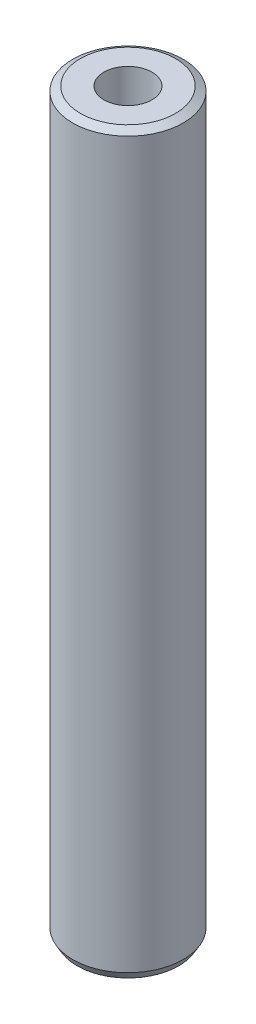
SolidWorks part; units mm, degrees
ref_plane "Front Plane" through (0, 0, 0) normal (0, 0, 1) x (1, 0, 0)
ref_plane "Top Plane" through (0, 0, 0) normal (0, 1, 0) x (1, 0, 0)
ref_plane "Right Plane" through (0, 0, 0) normal (1, 0, 0) x (0, 0, -1)
sketch "Sketch1" plane through (0, 0, 0) normal (0, 1, 0) x (1, 0, 0)
  circle A0 centre (0, 0) radius 45
  dimension "SHAFT_OD" = 90
extrude "Boss-Extrude1" add sketch "Sketch1" along normal blind 600
sketch "Sketch2" plane through (0, 0, 0) normal (0, 1, 0) x (1, 0, 0)
  circle A0 centre (0, 0) radius 19.588
  dimension "BORE_D" = 39.1761
extrude "Cut-Extrude1" cut sketch "Sketch2" along normal through all
chamfer "Chamfer1" distance 3.6153 angle 60 2 edges at (0, 600, 45) (0, 0, 45) first distance on face at (0, 600, 45) first distance on face at (0, 0, 19.588)
